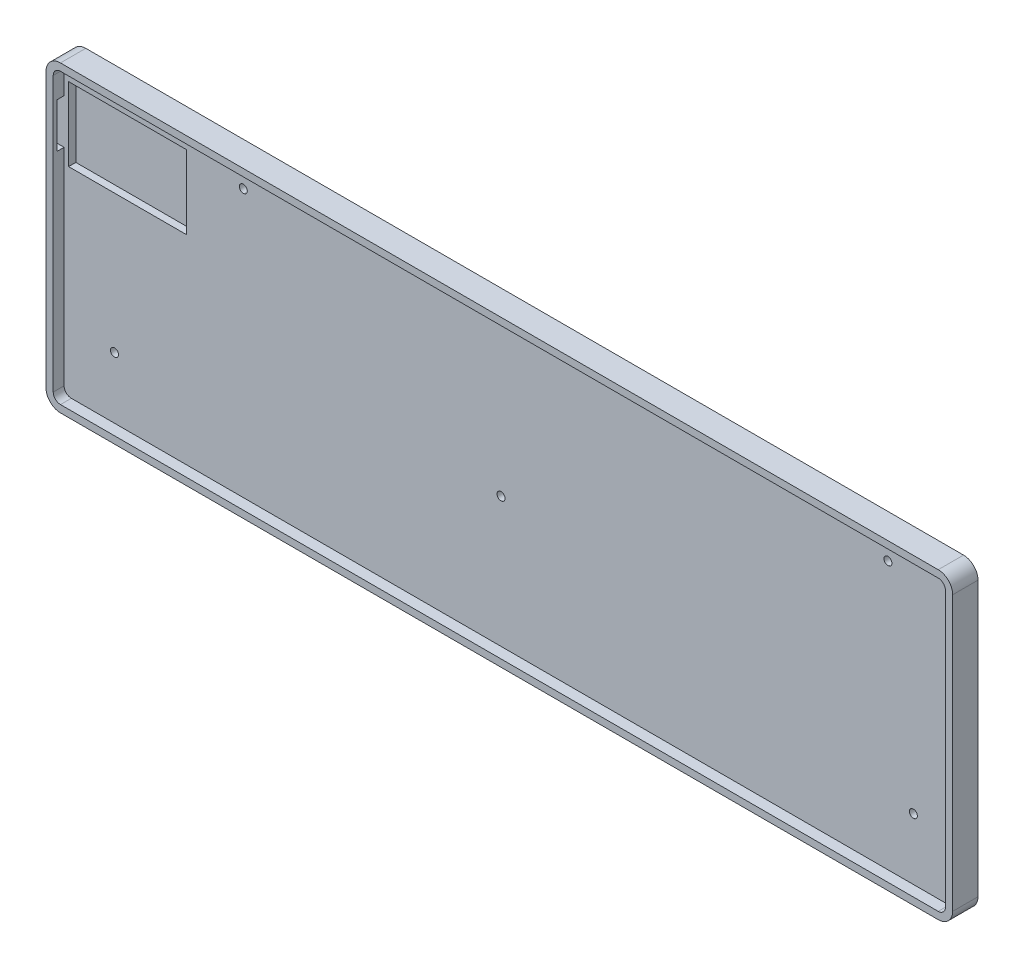
SolidWorks part; units mm, degrees
ref_plane "Front Plane" through (0, 0, 0) normal (0, 0, 1) x (1, 0, 0)
ref_plane "Top Plane" through (0, 0, 0) normal (0, 1, 0) x (1, 0, 0)
ref_plane "Right Plane" through (0, 0, 0) normal (1, 0, 0) x (0, 0, -1)
ref_plane "Plane1" through (0, 0, 1.6) normal (0, 0, 1) x (1, 0, 0)
sketch "Sketch1" plane through (0, 0, 1.6) normal (0, 0, 1) x (1, 0, 0)
  line L0 (342.62, -108.45) -> (99.95, -108.45)
  line L1 (97.95, -110.45) -> (97.95, -186.25)
  line L2 (99.95, -188.25) -> (342.62, -188.25)
  line L3 (344.62, -186.25) -> (344.62, -110.45)
  circle A0 centre (325.72, -114.3) radius 1.1
  circle A1 centre (330.8, -120) radius 0.95
  circle A2 centre (325.72, -120) radius 2.05
  circle A3 centre (320.64, -120) radius 0.95
  circle A4 centre (304.58, -120) radius 0.95
  circle A5 centre (299.5, -120) radius 2.05
  circle A6 centre (294.42, -120) radius 0.95
  circle A7 centre (285.58, -120) radius 0.95
  circle A8 centre (280.5, -120) radius 2.05
  circle A9 centre (329.53, -122.54) radius 1.5
  circle A10 centre (323.18, -125.08) radius 1.5
  circle A11 centre (327.37, -129) radius 0.15
  circle A12 centre (324.07, -129) radius 0.15
  circle A13 centre (303.31, -122.54) radius 1.5
  circle A14 centre (296.96, -125.08) radius 1.5
  circle A15 centre (284.31, -122.54) radius 1.5
  circle A16 centre (301.15, -129) radius 0.15
  circle A17 centre (297.85, -129) radius 0.15
  circle A18 centre (282.15, -129) radius 0.15
  circle A19 centre (275.42, -120) radius 0.95
  circle A20 centre (266.58, -120) radius 0.95
  circle A21 centre (261.5, -120) radius 2.05
  circle A22 centre (256.42, -120) radius 0.95
  circle A23 centre (247.58, -120) radius 0.95
  circle A24 centre (242.5, -120) radius 2.05
  circle A25 centre (237.42, -120) radius 0.95
  circle A26 centre (228.58, -120) radius 0.95
  circle A27 centre (223.5, -120) radius 2.05
  circle A28 centre (265.31, -122.54) radius 1.5
  circle A29 centre (277.96, -125.08) radius 1.5
  circle A30 centre (258.96, -125.08) radius 1.5
  circle A31 centre (278.85, -129) radius 0.15
  circle A32 centre (263.15, -129) radius 0.15
  circle A33 centre (259.85, -129) radius 0.15
  circle A34 centre (246.31, -122.54) radius 1.5
  circle A35 centre (239.96, -125.08) radius 1.5
  circle A36 centre (227.31, -122.54) radius 1.5
  circle A37 centre (220.96, -125.08) radius 1.5
  circle A38 centre (244.15, -129) radius 0.15
  circle A39 centre (240.85, -129) radius 0.15
  circle A40 centre (225.15, -129) radius 0.15
  circle A41 centre (221.85, -129) radius 0.15
  circle A42 centre (333.08, -139) radius 0.95
  circle A43 centre (328, -139) radius 2.05
  circle A44 centre (322.92, -139) radius 0.95
  circle A45 centre (309.33, -139) radius 0.95
  circle A46 centre (304.25, -139) radius 2.05
  circle A47 centre (299.17, -139) radius 0.95
  circle A48 centre (290.33, -139) radius 0.95
  circle A49 centre (285.25, -139) radius 2.05
  circle A50 centre (280.17, -139) radius 0.95
  circle A51 centre (331.81, -141.54) radius 1.5
  circle A52 centre (325.46, -144.08) radius 1.5
  circle A53 centre (329.65, -148) radius 0.15
  circle A54 centre (326.35, -148) radius 0.15
  circle A55 centre (308.06, -141.54) radius 1.5
  circle A56 centre (301.71, -144.08) radius 1.5
  circle A57 centre (289.06, -141.54) radius 1.5
  circle A58 centre (282.71, -144.08) radius 1.5
  circle A59 centre (305.9, -148) radius 0.15
  circle A60 centre (302.6, -148) radius 0.15
  circle A61 centre (286.9, -148) radius 0.15
  circle A62 centre (283.6, -148) radius 0.15
  circle A63 centre (271.33, -139) radius 0.95
  circle A64 centre (266.25, -139) radius 2.05
  circle A65 centre (261.17, -139) radius 0.95
  circle A66 centre (252.33, -139) radius 0.95
  circle A67 centre (247.25, -139) radius 2.05
  circle A68 centre (242.17, -139) radius 0.95
  circle A69 centre (233.33, -139) radius 0.95
  circle A70 centre (228.25, -139) radius 2.05
  circle A71 centre (223.17, -139) radius 0.95
  circle A72 centre (270.06, -141.54) radius 1.5
  circle A73 centre (251.06, -141.54) radius 1.5
  circle A74 centre (263.71, -144.08) radius 1.5
  circle A75 centre (267.9, -148) radius 0.15
  circle A76 centre (264.6, -148) radius 0.15
  circle A77 centre (244.71, -144.08) radius 1.5
  circle A78 centre (232.06, -141.54) radius 1.5
  circle A79 centre (225.71, -144.08) radius 1.5
  circle A80 centre (248.9, -148) radius 0.15
  circle A81 centre (245.6, -148) radius 0.15
  circle A82 centre (229.9, -148) radius 0.15
  circle A83 centre (226.6, -148) radius 0.15
  circle A84 centre (218.42, -120) radius 0.95
  circle A85 centre (209.58, -120) radius 0.95
  circle A86 centre (204.5, -120) radius 2.05
  circle A87 centre (199.42, -120) radius 0.95
  circle A88 centre (190.58, -120) radius 0.95
  circle A89 centre (185.5, -120) radius 2.05
  circle A90 centre (180.42, -120) radius 0.95
  circle A91 centre (171.58, -120) radius 0.95
  circle A92 centre (166.5, -120) radius 2.05
  circle A93 centre (161.42, -120) radius 0.95
  circle A94 centre (208.31, -122.54) radius 1.5
  circle A95 centre (189.31, -122.54) radius 1.5
  circle A96 centre (201.96, -125.08) radius 1.5
  circle A97 centre (206.15, -129) radius 0.15
  circle A98 centre (202.85, -129) radius 0.15
  circle A99 centre (182.96, -125.08) radius 1.5
  circle A100 centre (170.31, -122.54) radius 1.5
  circle A101 centre (163.96, -125.08) radius 1.5
  circle A102 centre (187.15, -129) radius 0.15
  circle A103 centre (183.85, -129) radius 0.15
  circle A104 centre (168.15, -129) radius 0.15
  circle A105 centre (164.85, -129) radius 0.15
  circle A106 centre (147.5, -114.3) radius 1.1
  circle A107 centre (129.49, -115.23) radius 0.5
  circle A108 centre (152.58, -120) radius 0.95
  circle A109 centre (147.5, -120) radius 2.05
  circle A110 centre (142.42, -120) radius 0.95
  circle A111 centre (133.58, -120) radius 0.95
  circle A112 centre (126.95, -115.23) radius 0.5
  circle A113 centre (124.41, -115.23) radius 0.5
  circle A114 centre (121.87, -115.23) radius 0.5
  circle A115 centre (119.33, -115.23) radius 0.5
  circle A116 centre (116.79, -115.23) radius 0.5
  circle A117 centre (114.25, -115.23) radius 0.5
  circle A118 centre (111.71, -115.23) radius 0.5
  circle A119 centre (109.17, -115.23) radius 0.5
  circle A120 centre (106.63, -115.23) radius 0.5
  circle A121 centre (104.09, -115.23) radius 0.5
  circle A122 centre (101.55, -115.23) radius 0.5
  circle A123 centre (128.5, -120) radius 2.05
  circle A124 centre (123.42, -120) radius 0.95
  circle A125 centre (114.58, -120) radius 0.95
  circle A126 centre (120.05, -121.15) radius 0.15
  circle A127 centre (109.5, -120) radius 2.05
  circle A128 centre (104.42, -120) radius 0.95
  circle A129 centre (100.875, -120.825) radius 0.15
  circle A130 centre (151.31, -122.54) radius 1.5
  circle A131 centre (144.96, -125.08) radius 1.5
  circle A132 centre (132.31, -122.54) radius 1.5
  circle A133 centre (149.15, -129) radius 0.15
  circle A134 centre (145.85, -129) radius 0.15
  circle A135 centre (129.49, -130.47) radius 0.5
  circle A136 centre (120.05, -124.45) radius 0.15
  circle A137 centre (125.96, -125.08) radius 1.5
  circle A138 centre (113.31, -122.54) radius 1.5
  circle A139 centre (100.875, -124.125) radius 0.15
  circle A140 centre (106.96, -125.08) radius 1.5
  circle A141 centre (126.95, -130.47) radius 0.5
  circle A142 centre (124.41, -130.47) radius 0.5
  circle A143 centre (121.87, -130.47) radius 0.5
  circle A144 centre (119.33, -130.47) radius 0.5
  circle A145 centre (116.79, -130.47) radius 0.5
  circle A146 centre (114.25, -130.47) radius 0.5
  circle A147 centre (111.71, -130.47) radius 0.5
  circle A148 centre (109.17, -130.47) radius 0.5
  circle A149 centre (106.63, -130.47) radius 0.5
  circle A150 centre (104.09, -130.47) radius 0.5
  circle A151 centre (101.55, -130.47) radius 0.5
  circle A152 centre (214.33, -139) radius 0.95
  circle A153 centre (209.25, -139) radius 2.05
  circle A154 centre (204.17, -139) radius 0.95
  circle A155 centre (195.33, -139) radius 0.95
  circle A156 centre (190.25, -139) radius 2.05
  circle A157 centre (185.17, -139) radius 0.95
  circle A158 centre (176.33, -139) radius 0.95
  circle A159 centre (171.25, -139) radius 2.05
  circle A160 centre (166.17, -139) radius 0.95
  circle A161 centre (213.06, -141.54) radius 1.5
  circle A162 centre (206.71, -144.08) radius 1.5
  circle A163 centre (194.06, -141.54) radius 1.5
  circle A164 centre (210.9, -148) radius 0.15
  circle A165 centre (207.6, -148) radius 0.15
  circle A166 centre (191.9, -148) radius 0.15
  circle A167 centre (175.06, -141.54) radius 1.5
  circle A168 centre (187.71, -144.08) radius 1.5
  circle A169 centre (168.71, -144.08) radius 1.5
  circle A170 centre (188.6, -148) radius 0.15
  circle A171 centre (172.9, -148) radius 0.15
  circle A172 centre (169.6, -148) radius 0.15
  circle A173 centre (157.33, -139) radius 0.95
  circle A174 centre (152.25, -139) radius 2.05
  circle A175 centre (147.17, -139) radius 0.95
  circle A176 centre (138.33, -139) radius 0.95
  circle A177 centre (133.25, -139) radius 2.05
  circle A178 centre (128.17, -139) radius 0.95
  circle A179 centre (116.955, -139) radius 0.95
  circle A180 centre (99.78, -137.775) radius 0.45
  circle A181 centre (111.875, -139) radius 2.05
  circle A182 centre (106.795, -139) radius 0.95
  circle A183 centre (99.78, -140.775) radius 0.45
  circle A184 centre (156.06, -141.54) radius 1.5
  circle A185 centre (149.71, -144.08) radius 1.5
  circle A186 centre (137.06, -141.54) radius 1.5
  circle A187 centre (130.71, -144.08) radius 1.5
  circle A188 centre (153.9, -148) radius 0.15
  circle A189 centre (150.6, -148) radius 0.15
  circle A190 centre (134.9, -148) radius 0.15
  circle A191 centre (131.6, -148) radius 0.15
  circle A192 centre (115.685, -141.54) radius 1.5
  circle A193 centre (109.335, -144.08) radius 1.5
  circle A194 centre (113.525, -148) radius 0.15
  circle A195 centre (110.225, -148) radius 0.15
  circle A196 centre (337.83, -158) radius 0.95
  circle A197 centre (332.75, -158) radius 2.05
  circle A198 centre (327.67, -158) radius 0.95
  circle A199 centre (318.83, -158) radius 0.95
  circle A200 centre (313.75, -158) radius 2.05
  circle A201 centre (308.67, -158) radius 0.95
  circle A202 centre (299.83, -158) radius 0.95
  circle A203 centre (294.75, -158) radius 2.05
  circle A204 centre (289.67, -158) radius 0.95
  circle A205 centre (280.83, -158) radius 0.95
  circle A206 centre (336.56, -160.54) radius 1.5
  circle A207 centre (330.21, -163.08) radius 1.5
  circle A208 centre (317.56, -160.54) radius 1.5
  circle A209 centre (311.21, -163.08) radius 1.5
  circle A210 centre (334.4, -167) radius 0.15
  circle A211 centre (331.1, -167) radius 0.15
  circle A212 centre (315.4, -167) radius 0.15
  circle A213 centre (312.1, -167) radius 0.15
  circle A214 centre (298.56, -160.54) radius 1.5
  circle A215 centre (279.56, -160.54) radius 1.5
  circle A216 centre (292.21, -163.08) radius 1.5
  circle A217 centre (296.4, -167) radius 0.15
  circle A218 centre (293.1, -167) radius 0.15
  circle A219 centre (275.75, -158) radius 2.05
  circle A220 centre (270.67, -158) radius 0.95
  circle A221 centre (261.83, -158) radius 0.95
  circle A222 centre (256.75, -158) radius 2.05
  circle A223 centre (251.67, -158) radius 0.95
  circle A224 centre (242.83, -158) radius 0.95
  circle A225 centre (237.75, -158) radius 2.05
  circle A226 centre (232.67, -158) radius 0.95
  circle A227 centre (223.83, -158) radius 0.95
  circle A228 centre (273.21, -163.08) radius 1.5
  circle A229 centre (260.56, -160.54) radius 1.5
  circle A230 centre (254.21, -163.08) radius 1.5
  circle A231 centre (277.4, -167) radius 0.15
  circle A232 centre (274.1, -167) radius 0.15
  circle A233 centre (258.4, -167) radius 0.15
  circle A234 centre (255.1, -167) radius 0.15
  circle A235 centre (241.56, -160.54) radius 1.5
  circle A236 centre (235.21, -163.08) radius 1.5
  circle A237 centre (222.56, -160.54) radius 1.5
  circle A238 centre (239.4, -167) radius 0.15
  circle A239 centre (236.1, -167) radius 0.15
  circle A240 centre (220.4, -167) radius 0.15
  circle A241 centre (332.75, -171.3) radius 1.1
  circle A242 centre (337.83, -177) radius 0.95
  circle A243 centre (332.75, -177) radius 2.05
  circle A244 centre (327.67, -177) radius 0.95
  circle A245 centre (318.83, -177) radius 0.95
  circle A246 centre (313.75, -177) radius 2.05
  circle A247 centre (308.67, -177) radius 0.95
  circle A248 centre (299.83, -177) radius 0.95
  circle A249 centre (294.75, -177) radius 2.05
  circle A250 centre (289.67, -177) radius 0.95
  circle A251 centre (280.83, -177) radius 0.95
  circle A252 centre (336.56, -179.54) radius 1.5
  circle A253 centre (330.21, -182.08) radius 1.5
  circle A254 centre (317.56, -179.54) radius 1.5
  circle A255 centre (311.21, -182.08) radius 1.5
  circle A256 centre (334.4, -186) radius 0.15
  circle A257 centre (331.1, -186) radius 0.15
  circle A258 centre (315.4, -186) radius 0.15
  circle A259 centre (312.1, -186) radius 0.15
  circle A260 centre (298.56, -179.54) radius 1.5
  circle A261 centre (279.56, -179.54) radius 1.5
  circle A262 centre (292.21, -182.08) radius 1.5
  circle A263 centre (296.4, -186) radius 0.15
  circle A264 centre (293.1, -186) radius 0.15
  circle A265 centre (256.813, -170.015) radius 1.524
  circle A266 centre (275.75, -177) radius 2.05
  circle A267 centre (270.67, -177) radius 0.95
  circle A268 centre (249.955, -177) radius 0.95
  circle A269 centre (232.937, -170.015) radius 1.524
  circle A270 centre (244.875, -177) radius 2.05
  circle A271 centre (239.795, -177) radius 0.95
  circle A272 centre (273.21, -182.08) radius 1.5
  circle A273 centre (277.4, -186) radius 0.15
  circle A274 centre (274.1, -186) radius 0.15
  circle A275 centre (256.813, -185.225) radius 1.9939
  circle A276 centre (248.685, -179.54) radius 1.5
  circle A277 centre (242.335, -182.08) radius 1.5
  circle A278 centre (246.525, -186) radius 0.15
  circle A279 centre (243.225, -186) radius 0.15
  circle A280 centre (232.937, -185.225) radius 1.9939
  circle A281 centre (218.75, -152.3) radius 1.1
  circle A282 centre (218.75, -158) radius 2.05
  circle A283 centre (213.67, -158) radius 0.95
  circle A284 centre (204.83, -158) radius 0.95
  circle A285 centre (199.75, -158) radius 2.05
  circle A286 centre (194.67, -158) radius 0.95
  circle A287 centre (185.83, -158) radius 0.95
  circle A288 centre (180.75, -158) radius 2.05
  circle A289 centre (175.67, -158) radius 0.95
  circle A290 centre (166.83, -158) radius 0.95
  circle A291 centre (161.75, -158) radius 2.05
  circle A292 centre (216.21, -163.08) radius 1.5
  circle A293 centre (203.56, -160.54) radius 1.5
  circle A294 centre (197.21, -163.08) radius 1.5
  circle A295 centre (217.1, -167) radius 0.15
  circle A296 centre (201.4, -167) radius 0.15
  circle A297 centre (198.1, -167) radius 0.15
  circle A298 centre (184.56, -160.54) radius 1.5
  circle A299 centre (178.21, -163.08) radius 1.5
  circle A300 centre (165.56, -160.54) radius 1.5
  circle A301 centre (159.21, -163.08) radius 1.5
  circle A302 centre (182.4, -167) radius 0.15
  circle A303 centre (179.1, -167) radius 0.15
  circle A304 centre (163.4, -167) radius 0.15
  circle A305 centre (160.1, -167) radius 0.15
  circle A306 centre (130.6, -154.325) radius 0.375
  circle A307 centre (156.67, -158) radius 0.95
  circle A308 centre (147.83, -158) radius 0.95
  circle A309 centre (142.75, -158) radius 2.05
  circle A310 centre (137.67, -158) radius 0.95
  circle A311 centre (128.6, -154.325) radius 0.375
  circle A312 centre (121.705, -158) radius 0.95
  circle A313 centre (116.625, -158) radius 2.05
  circle A314 centre (111.545, -158) radius 0.95
  circle A315 centre (146.56, -160.54) radius 1.5
  circle A316 centre (140.21, -163.08) radius 1.5
  circle A317 centre (144.4, -167) radius 0.15
  circle A318 centre (141.1, -167) radius 0.15
  circle A319 centre (120.435, -160.54) radius 1.5
  circle A320 centre (114.085, -163.08) radius 1.5
  circle A321 centre (118.275, -167) radius 0.15
  circle A322 centre (114.975, -167) radius 0.15
  circle A323 centre (209.313, -170.04) radius 1.524
  circle A324 centre (202.455, -177) radius 0.95
  circle A325 centre (197.375, -177) radius 2.05
  circle A326 centre (192.295, -177) radius 0.95
  circle A327 centre (185.437, -170.04) radius 1.524
  circle A328 centre (164.455, -177) radius 0.95
  circle A329 centre (159.375, -177) radius 2.05
  circle A330 centre (201.185, -179.54) radius 1.5
  circle A331 centre (194.835, -182.08) radius 1.5
  circle A332 centre (209.313, -185.25) radius 1.9939
  circle A333 centre (199.025, -186) radius 0.15
  circle A334 centre (195.725, -186) radius 0.15
  circle A335 centre (163.185, -179.54) radius 1.5
  circle A336 centre (185.437, -185.25) radius 1.9939
  circle A337 centre (161.025, -186) radius 0.15
  circle A338 centre (154.295, -177) radius 0.95
  circle A339 centre (140.705, -177) radius 0.95
  circle A340 centre (135.625, -177) radius 2.05
  circle A341 centre (130.545, -177) radius 0.95
  circle A342 centre (111.875, -171.3) radius 1.1
  circle A343 centre (116.955, -177) radius 0.95
  circle A344 centre (111.875, -177) radius 2.05
  circle A345 centre (106.795, -177) radius 0.95
  circle A346 centre (156.835, -182.08) radius 1.5
  circle A347 centre (139.435, -179.54) radius 1.5
  circle A348 centre (133.085, -182.08) radius 1.5
  circle A349 centre (157.725, -186) radius 0.15
  circle A350 centre (137.275, -186) radius 0.15
  circle A351 centre (133.975, -186) radius 0.15
  circle A352 centre (115.685, -179.54) radius 1.5
  circle A353 centre (109.335, -182.08) radius 1.5
  circle A354 centre (113.525, -186) radius 0.15
  circle A355 centre (110.225, -186) radius 0.15
  arc A356 (344.62, -110.45) -> (342.62, -108.45) centre (342.62, -110.45) ccw
  arc A357 (99.95, -108.45) -> (97.95, -110.45) centre (99.95, -110.45) ccw
  arc A358 (97.95, -186.25) -> (99.95, -188.25) centre (99.95, -186.25) ccw
  arc A359 (342.62, -188.25) -> (344.62, -186.25) centre (342.62, -186.25) ccw
extrude "Boss-Extrude1" add sketch "Sketch1" against normal blind 1.6
sketch "Sketch2" plane through (0, 0, 1.6) normal (0, 0, 1) x (1, 0, 0)
  line L0 (99.95, -108.45) -> (342.62, -108.45)
  line L1 (344.62, -110.45) -> (344.62, -186.25)
  line L2 (342.62, -188.25) -> (99.95, -188.25)
  line L3 (97.95, -186.25) -> (97.95, -110.45)
  line L4 (97.95, -110.45) -> (97.95, -186.25)
  line L5 (99.95, -106.45) -> (342.62, -106.45)
  line L6 (346.62, -110.45) -> (346.62, -186.25)
  line L7 (342.62, -190.25) -> (99.95, -190.25)
  line L8 (95.95, -110.45) -> (95.95, -186.25)
  circle A0 centre (147.5, -114.3) radius 1.1
  circle A1 centre (325.72, -114.3) radius 1.1
  circle A2 centre (332.75, -171.3) radius 1.1
  circle A3 centre (218.75, -152.3) radius 1.1138
  circle A4 centre (111.875, -171.3) radius 1.106
  arc A5 (342.62, -108.45) -> (344.62, -110.45) centre (342.62, -110.45) cw
  arc A6 (344.62, -186.25) -> (342.62, -188.25) centre (342.62, -186.25) cw
  arc A7 (99.95, -188.25) -> (97.95, -186.25) centre (99.95, -186.25) cw
  arc A8 (97.95, -110.45) -> (99.95, -108.45) centre (99.95, -110.45) cw
  arc A9 (95.95, -110.45) -> (99.95, -106.45) centre (99.95, -110.45) cw
  arc A10 (342.62, -106.45) -> (346.62, -110.45) centre (342.62, -110.45) cw
  arc A11 (346.62, -186.25) -> (342.62, -190.25) centre (342.62, -186.25) cw
  arc A12 (99.95, -190.25) -> (95.95, -186.25) centre (99.95, -186.25) cw
  dimension "D1" = 2
extrude "Boss-Extrude2" add sketch "Sketch2" along normal blind 5 and the other way blind 2 separate body contours A12 L7 A11 L6 A10 L5 A9 L8 L3 A8 L0 A5 L1 A6 L2 A7 region at (221.285, -106.7143, 1.6)
sketch "Sketch5" plane through (0, 0, 0) normal (0, 0, 1) x (1, 0, 0)
  line L0 (99.95, -108.45) -> (342.62, -108.45)
  line L1 (344.62, -110.45) -> (344.62, -186.25)
  line L2 (342.62, -188.25) -> (99.95, -188.25)
  line L3 (97.95, -186.25) -> (97.95, -110.45)
  line L4 (97.95, -110.45) -> (97.95, -186.25)
  line L5 (99.95, -106.45) -> (342.62, -106.45)
  line L6 (346.62, -110.45) -> (346.62, -186.25)
  line L7 (342.62, -190.25) -> (99.95, -190.25)
  line L8 (95.95, -110.45) -> (95.95, -186.25)
  circle A0 centre (147.5, -114.3) radius 1.1
  circle A1 centre (325.72, -114.3) radius 1.1
  circle A2 centre (332.75, -171.3) radius 1.1
  circle A3 centre (218.75, -152.3) radius 1.1138
  circle A4 centre (111.875, -171.3) radius 1.106
  arc A5 (342.62, -108.45) -> (344.62, -110.45) centre (342.62, -110.45) cw
  arc A6 (344.62, -186.25) -> (342.62, -188.25) centre (342.62, -186.25) cw
  arc A7 (99.95, -188.25) -> (97.95, -186.25) centre (99.95, -186.25) cw
  arc A8 (97.95, -110.45) -> (99.95, -108.45) centre (99.95, -110.45) cw
  arc A9 (95.95, -110.45) -> (99.95, -106.45) centre (99.95, -110.45) cw
  arc A10 (342.62, -106.45) -> (346.62, -110.45) centre (342.62, -110.45) cw
  arc A11 (346.62, -186.25) -> (342.62, -190.25) centre (342.62, -186.25) cw
  arc A12 (99.95, -190.25) -> (95.95, -186.25) centre (99.95, -186.25) cw
  point P47 (0, 0)
  dimension "D1" = 2
extrude "Boss-Extrude5" add sketch "Sketch5" along normal blind 2 and the other way blind 2 from offset 1.6 contours A8 L3 A7 L2 A6 L1 A5 L0 A4 A3 A2 A1 A0 region at (221.2794, -148.3535, 0)
sketch "Sketch6" plane through (0, 0, 3.6) normal (0, 0, 1) x (1, 0, 0)
  line L1 (131.7363, -112.7927) -> (99.2016, -112.7927)
  line L2 (131.7363, -112.7927) -> (131.7363, -133.1474)
  line L3 (131.7363, -133.1474) -> (99.2016, -133.1474)
  line L4 (99.2016, -112.7927) -> (99.2016, -133.1474)
  point P4 (99.2016, -133.1474)
extrude "Cut-Extrude1" cut sketch "Sketch6" against normal blind 2
sketch "Sketch7" plane through (99.2016, 0, 0) normal (1, 0, 0) x (0, 0, -1)
  line L0 (-1.6, 96.4207) -> (-1.6, -96.4207) construction
  line L1 (-1.6, -116.7927) -> (-5.6, -116.7927)
  line L2 (-1.6, -116.7927) -> (-1.6, -129.1474)
  line L3 (-1.6, -129.1474) -> (-5.6, -129.1474)
  line L4 (-5.6, -116.7927) -> (-5.6, -129.1474)
  line L5 (-1.6, -112.7927) -> (-1.6, -133.1474)
  line L6 (-1.6, -112.7927) -> (-3.6, -112.7927) construction
  line L7 (-1.6, -112.7927) -> (-1.6, -133.1474) construction
  line L8 (-1.6, -133.1474) -> (-3.6, -133.1474) construction
  line M5 (-3.6, -112.7927) -> (-3.6, -133.1474)
  dimension "D1" = 4
  dimension "D2" = 4
extrude "Cut-Extrude2" cut sketch "Sketch7" against normal through all contours L1 L4 L3 M5 region at (99.2016, -122.9701, 4.6)
